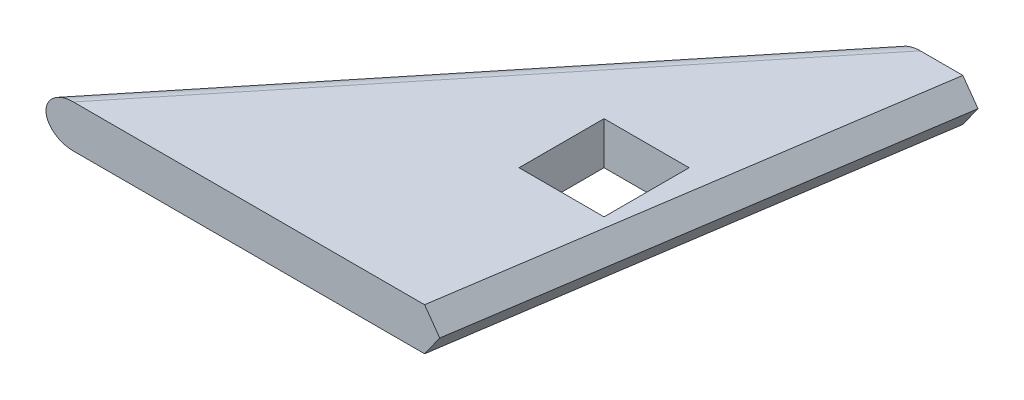
SolidWorks part; units mm, degrees
material "Polyurethane Foam Rigid"
ref_plane "Front Plane" through (0, 0, 0) normal (0, 0, 1) x (1, 0, 0)
ref_plane "Top Plane" through (0, 0, 0) normal (0, 1, 0) x (1, 0, 0)
ref_plane "Right Plane" through (0, 0, 0) normal (1, 0, 0) x (0, 0, -1)
sketch "Sketch1" plane through (0, 0, 0) normal (0, 1, 0) x (1, 0, 0)
  line L0 (0, 0) -> (455.7968, 0) construction
  line L1 (0, 0) -> (150.368, 0)
  line L2 (0, 0) -> (0, 139.7) construction
  line L3 (0, 139.7) -> (226.5295, 139.7) construction
  line L4 (37.592, 0) -> (128.3142, 139.7)
  line L5 (0, 0) -> (113.2647, 139.7)
  line L6 (113.2647, 139.7) -> (173.4627, 139.7)
  line L7 (150.368, 0) -> (173.4627, 139.7)
  point P4 (37.592, 0)
  dimension "D1" = 150.368
  dimension "D2" = 139.7
  dimension "D3" = 37.592
  dimension "D4" = 33
  dimension "D5" = 15.0495
  dimension "D6" = 60.198
extrude "Boss-Extrude1" add sketch "Sketch1" along normal blind 12.7 contours L1 L7 L6 L4 | L6 L5 L1 L4 region at (62.5134, 0, -59.8795) region at (118.3726, 0, -59.8795)
sketch "rudder" plane through (0, 12.7, 0) normal (0, 1, 0) x (1, 0, 0)
  line L0 (113.2647, 139.7) -> (173.4627, 139.7) construction
  line L5 (153.6507, 139.7) -> (130.556, 0)
  line L6 (0, 0) -> (150.368, 0) construction
  line L7 (150.368, 0) -> (173.4627, 139.7) construction
  line L8 (153.6507, 139.7) -> (173.4627, 139.7)
  line L9 (173.4627, 139.7) -> (150.368, 0)
  line L10 (150.368, 0) -> (130.556, 0)
  point P0 (153.6507, 139.7)
  dimension "D1" = 19.812
sketch "Sketch3" plane through (0, 12.7, 0) normal (0, 1, 0) x (1, 0, 0)
  line L0 (142.1034, 69.85) -> (56.6324, 69.85) construction
  line L1 (153.6507, 139.7) -> (130.556, 0) construction
  line L2 (0, 0) -> (113.2647, 139.7) construction
  line L4 (91.7479, 74.93) -> (117.1479, 74.93)
  line L5 (91.7479, 74.93) -> (91.7479, 49.53)
  line L6 (91.7479, 49.53) -> (117.1479, 49.53)
  line L7 (117.1479, 74.93) -> (117.1479, 49.53)
  point P6 (99.3679, 69.85)
  dimension "D1" = 25.4
  dimension "D2" = 25.4
  dimension "D3" = 7.62
  dimension "D4" = 5.08
extrude "servo hole" cut sketch "Sketch3" against normal through all both
fillet "Fillet1" radius 6.35 2 edges at (56.6324, 0, -69.85) (56.6324, 12.7, -69.85)
sketch "Sketch4" plane through (0, 0, -139.7) normal (0, 0, -1) x (-1, 0, 0)
  line L1 (-134.1396, 0) -> (-138.6647, 6.35)
  line L2 (-121.4396, 0) -> (-173.4627, 0) construction
  line L3 (-138.6647, 6.35) -> (-134.1396, 12.7)
  line L4 (-121.4396, 12.7) -> (-173.4627, 12.7) construction
  line L5 (-138.6647, 12.7) -> (-138.6647, 0) construction
  line L6 (-173.4627, 12.7) -> (-173.4627, 0)
  line L7 (-173.4627, 0) -> (-134.1396, 0)
  line L8 (-173.4627, 12.7) -> (-134.1396, 12.7)
  dimension "D1" = 25.4
  dimension "D2" = 12.7
  dimension "D3" = 12.7
extrude "Cut-Extrude1" cut sketch "Sketch4" against normal through all both draft 7 draft outward yes
